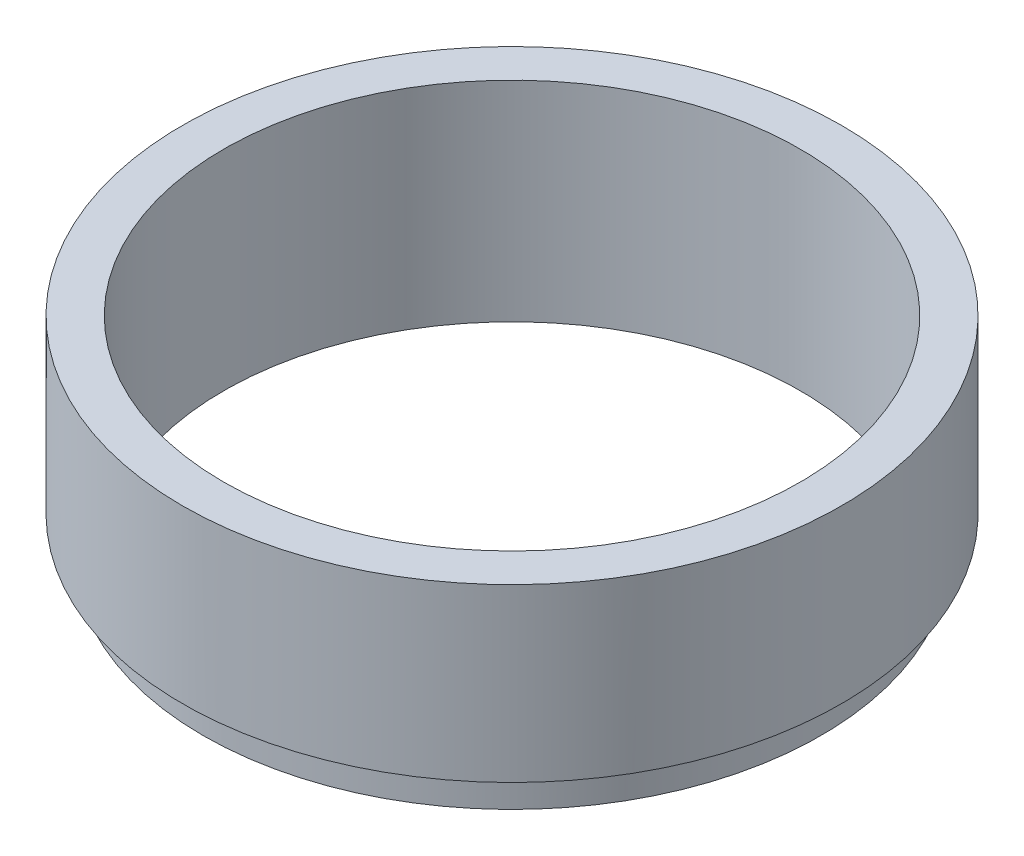
SolidWorks part; units mm, degrees
material "C (Graphite)"
ref_plane "Front Plane" through (0, 0, 0) normal (0, 0, 1) x (1, 0, 0)
ref_plane "Top Plane" through (0, 0, 0) normal (0, 1, 0) x (1, 0, 0)
ref_plane "Right Plane" through (0, 0, 0) normal (1, 0, 0) x (0, 0, -1)
sketch "Sketch1" plane through (0, 0, 0) normal (0, 1, 0) x (1, 0, 0)
  circle A0 centre (0, 0) radius 40
  circle A1 centre (0, 0) radius 35
  dimension "D1" = 80
  dimension "D2" = 70
extrude "Boss-Extrude1" add sketch "Sketch1" along normal blind 25.4
sketch "Sketch2" plane through (0, 0, 0) normal (0, -1, 0) x (1, 0, 0)
  circle A0 centre (0, 0) radius 37.5
  circle A1 centre (0, 0) radius 40
  dimension "D1" = 75
  dimension "D2" = 80
extrude "Cut-Extrude1" cut sketch "Sketch2" against normal blind 4.6
